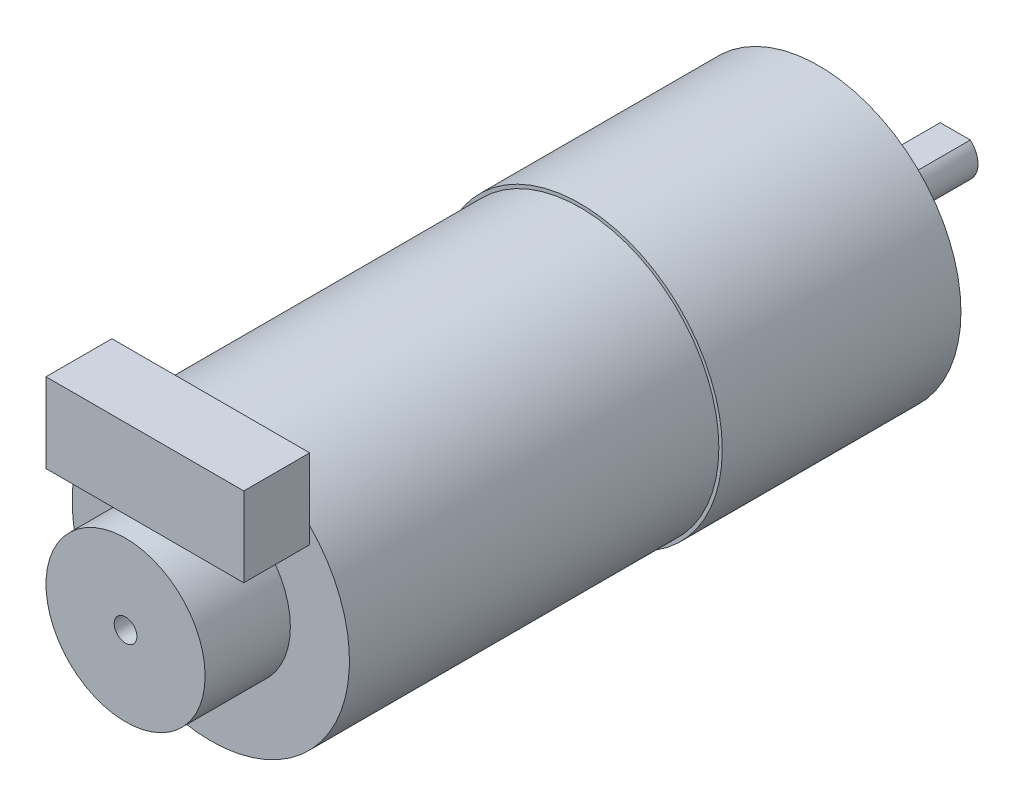
SolidWorks part; units mm, degrees
ref_plane "Front Plane" through (0, 0, 0) normal (0, 0, 1) x (1, 0, 0)
ref_plane "Top Plane" through (0, 0, 0) normal (0, 1, 0) x (1, 0, 0)
ref_plane "Right Plane" through (0, 0, 0) normal (1, 0, 0) x (0, 0, -1)
sketch "Sketch1" plane through (0, 0, 0) normal (0, 0, 1) x (1, 0, 0)
  circle A0 centre (0, 0) radius 2
extrude "Boss-Extrude1" add sketch "Sketch1" along normal blind 9.5
sketch "Sketch3" plane through (0, 0, 9.5) normal (0, 0, 1) x (1, 0, 0)
  circle A0 centre (0, 0) radius 3.5
extrude "Boss-Extrude2" add sketch "Sketch3" along normal blind 2.5
sketch "Sketch4" plane through (0, 0, 12) normal (0, 0, 1) x (1, 0, 0)
  circle A0 centre (0, 0) radius 12.5
extrude "Boss-Extrude3" add sketch "Sketch4" along normal blind 21
sketch "Sketch5" plane through (0, 0, 33) normal (0, 0, 1) x (1, 0, 0)
  circle A0 centre (0, 0) radius 12.2
extrude "Boss-Extrude4" add sketch "Sketch5" along normal blind 32.5
sketch "Sketch6" plane through (0, 0, 65.5) normal (0, 0, 1) x (1, 0, 0)
  circle A0 centre (0, 0) radius 7
extrude "Boss-Extrude5" add sketch "Sketch6" along normal blind 7.5
sketch "Sketch7" plane through (0, 0, 0) normal (0, 0, -1) x (-1, 0, 0)
  line L1 (0, 1.5) -> (1.3229, 1.5)
  line L2 (0, 1.5) -> (-1.3229, 1.5)
  arc A0 (1.3229, 1.5) -> (-1.3229, 1.5) centre (0, 0) ccw
extrude "Cut-Extrude1" cut sketch "Sketch7" against normal blind 8
sketch "Sketch8" plane through (0, 0, 12) normal (0, 0, -1) x (-1, 0, 0)
  circle A0 centre (8.5, 0) radius 3
  circle A1 centre (0, -8.5) radius 3
  circle A2 centre (-8.5, 0) radius 3
  circle A3 centre (0, 8.5) radius 3
  point P11 (0, 0)
  dimension "D1" = 4
extrude "Cut-Extrude2" cut sketch "Sketch8" against normal blind 5
thread "Thread1" pitch 0.5 method extrude profile "Thread Profile1" start angle 0, offset 0, length 5, pitch 0.5, diameter 6
ref_plane "Plane1" through (5.5, 0, 17) normal (0, -1, 0) x (-1, 0, 0)
sketch "Thread Profile1" plane through (5.5, 0, 17) normal (0, -1, 0) x (-1, 0, 0)
  line L0 (0, 0) -> (0, 0.5) construction
  line L11 (0, 0) -> (0, 0.4375)
  line L12 (0, 0.4375) -> (-0.2706, 0.2812)
  line L13 (-0.2706, 0.2812) -> (-0.2706, 0.1562)
  line L15 (-0.2706, 0.1562) -> (0, 0)
  line L17 (-0.2706, 0.2187) -> (0, 0.2187) construction
  point P2 (0, 0)
  dimension "Pitch" = 0.5
  dimension "Profile_Angle" = 60
  dimension "Profile_Land" = 0.125
  dimension "Profile_Height" = 0.2706
thread "Thread2" pitch 0.5 method extrude profile "Thread Profile2" start angle 0, offset 0, length 5, pitch 0.5, diameter 6
ref_plane "Plane2" through (-11.5, 0, 17) normal (0, -1, 0) x (-1, 0, 0)
sketch "Thread Profile2" plane through (-11.5, 0, 17) normal (0, -1, 0) x (-1, 0, 0)
  line L0 (0, 0) -> (0, 0.5) construction
  line L11 (0, 0) -> (0, 0.4375)
  line L12 (0, 0.4375) -> (-0.2706, 0.2812)
  line L13 (-0.2706, 0.2812) -> (-0.2706, 0.1562)
  line L15 (-0.2706, 0.1562) -> (0, 0)
  line L17 (-0.2706, 0.2187) -> (0, 0.2187) construction
  point P2 (0, 0)
  dimension "Pitch" = 0.5
  dimension "Profile_Angle" = 60
  dimension "Profile_Land" = 0.125
  dimension "Profile_Height" = 0.2706
ref_plane "Plane3" through (0, 7.1, 0) normal (0, 1, 0) x (1, 0, 0)
sketch "Sketch16" plane through (0, 0, 65.5) normal (0, 0, 1) x (1, 0, 0)
  line L1 (13.75, 7.1) -> (-13.75, 7.1) construction
  line L2 (0, 7.1) -> (8.7, 7.1)
  line L3 (8.7, 7.1) -> (8.7, 14.1)
  line L4 (8.7, 14.1) -> (8.3, 14.1)
  line L5 (0, 7.1) -> (-8.7, 7.1)
  line L6 (-8.7, 7.1) -> (-8.7, 14.1)
  line L7 (-8.7, 14.1) -> (8.3, 14.1)
extrude "Boss-Extrude11" add sketch "Sketch16" along normal blind 5.8
sketch "Sketch17" plane through (0, 0, 73) normal (0, 0, 1) x (1, 0, 0)
  circle A0 centre (0, 0) radius 1
extrude "Cut-Extrude3" cut sketch "Sketch17" against normal blind 3
